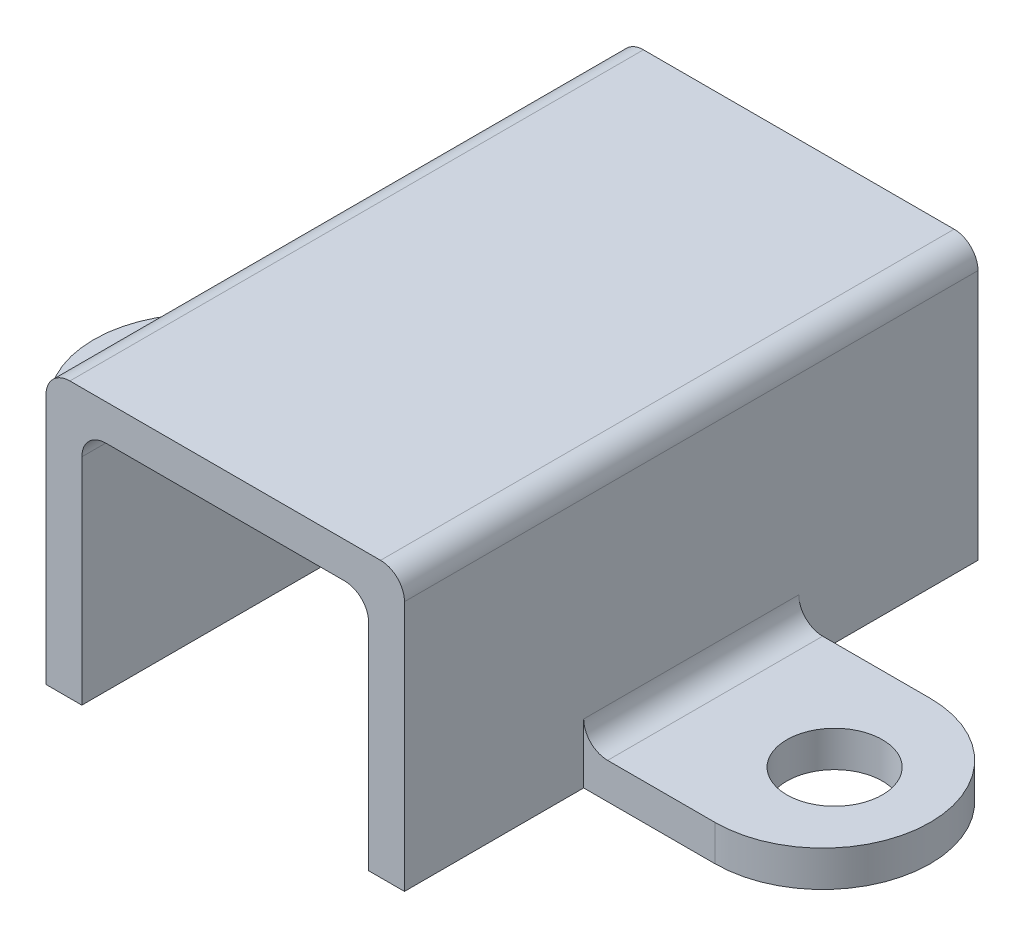
SolidWorks part; units mm, degrees
material "Moldeo de estratificados"
ref_plane "Alzado" through (0, 0, 0) normal (0, 0, 1) x (1, 0, 0)
ref_plane "Planta" through (0, 0, 0) normal (0, 1, 0) x (1, 0, 0)
ref_plane "Vista lateral" through (0, 0, 0) normal (1, 0, 0) x (0, 0, -1)
sketch "Croquis1" plane through (0, 0, 0) normal (0, 0, 1) x (1, 0, 0)
  line L0 (-17.5, -11.5) -> (-17.5, -10)
  line L1 (-17.5, -11.5) -> (-6, -11.5)
  line L2 (-6, -11.5) -> (-6, -1.5)
  line L3 (-6, -1.5) -> (6, -1.5)
  line L4 (6, -1.5) -> (6, -11.5)
  line L5 (6, -11.5) -> (17.5, -11.5)
  line L6 (-17.5, -10) -> (-7.5, -10)
  line L7 (-7.5, -10) -> (-7.5, 0)
  line L8 (-7.5, 0) -> (7.5, 0)
  line L9 (7.5, 0) -> (7.5, -10)
  line L10 (7.5, -10) -> (17.5, -10)
  line L11 (17.5, -10) -> (17.5, -11.5)
  line L12 (0, 6.6473) -> (0, -22.2046) construction
  point P10 (0, 0)
  dimension "D1" = 1.5
  dimension "D2" = 1.5
  dimension "D3" = 1.5
  dimension "D4" = 10
  dimension "D5" = 1.5
  dimension "D6" = 1.5
  dimension "D7" = 6
  dimension "D8" = 17.5
  dimension "D9" = 17.5
extrude "Saliente-Extruir2" add sketch "Croquis1" along normal mid plane 24
sketch "Croquis4" plane through (0, -10, 0) normal (0, 1, 0) x (1, 0, 0)
  line L0 (-28.0622, 0) -> (28.0622, 0) construction
  line L1 (-7.5, 4.5) -> (-7.5, -4.5)
  line L2 (7.5, 4.5) -> (7.5, -4.5)
  line L3 (-7.5, -12) -> (-7.5, 12) construction
  line L4 (7.5, -12) -> (7.5, 12) construction
  line L5 (-7.5, 4.5) -> (-17.5, 4.5)
  line L6 (-17.5, -12) -> (-17.5, 12) construction
  line L7 (-17.5, 4.5) -> (-17.5, -4.5)
  line L8 (-17.5, -4.5) -> (-7.5, -4.5)
  line L9 (-17.5, 12) -> (-7.5, 12)
  line L10 (-7.5, 12) -> (-7.5, 4.5)
  line L11 (-7.5, -4.5) -> (-7.5, -12)
  line L12 (-7.5, -12) -> (-17.5, -12)
  line L13 (-17.5, -12) -> (-17.5, -4.5)
  line L14 (-17.5, 12) -> (-17.5, 4.5)
  line L15 (17.5, 4.5) -> (17.5, -4.5)
  line L16 (7.5, 4.5) -> (17.5, 4.5)
  line L17 (7.5, 4.5) -> (7.5, 12)
  line L18 (7.5, 12) -> (17.5, 12)
  line L19 (17.5, 4.5) -> (17.5, 12)
  line L20 (7.5, -4.5) -> (17.5, -4.5)
  line L21 (7.5, -4.5) -> (7.5, -12)
  line L22 (7.5, -12) -> (17.5, -12)
  line L23 (17.5, -4.5) -> (17.5, -12)
  circle A0 centre (-13.5, 0) radius 2
  circle A1 centre (13.5, 0) radius 2
  point P9 (7.5, 0)
  point P10 (0, 0)
  point P11 (-7.5, 0)
  line M3 (-7.5, 12) -> (-17.5, 12)
  line M4 (-17.5, 12) -> (-17.5, -12)
  line M5 (-17.5, -12) -> (-7.5, -12)
  line M6 (-7.5, -12) -> (-7.5, 12)
  dimension "D1" = 4
  dimension "D2" = 13.5
  dimension "D3" = 13.5
  dimension "D4" = 9
extrude "Cortar-Extruir2" cut sketch "Croquis4" against normal through all contours L5 M6 M3 M4 | L16 L19 L18 L17 | L23 L20 L21 L22 | L8 M4 M5 M6 region at (-12.5, -10, -8.25) region at (-12.5, -10, 8.25) region at (12.5, -10, -8.25) region at (12.5, -10, 8.25)
sketch "Croquis6" plane through (0, -10, 0) normal (0, 1, 0) x (1, 0, 0)
  line L0 (-21.4058, 0) -> (22.0654, 0) construction
  circle A0 centre (-13.5, 0) radius 2
  circle A1 centre (13.5, 0) radius 2
  dimension "D1" = 4
  dimension "D2" = 13.5
  dimension "D3" = 13.5
extrude "Cortar-Extruir3" cut sketch "Croquis6" against normal through all
sketch "Croquis7" plane through (0, -10, 0) normal (0, 1, 0) x (1, 0, 0)
  line L0 (-13, 0) -> (-5.034, 0) construction
  line L6 (-17.5, -4.5) -> (-17.5, 4.5) construction
  line L7 (-13, 4.5) -> (-17.5, 4.5)
  line L8 (-17.5, 4.5) -> (-17.5, 0)
  line L9 (-17.5, 4.5) -> (-13, 4.5)
  line L10 (-17.5, 0) -> (-17.5, -4.5)
  line L11 (-17.5, -4.5) -> (-13, -4.5)
  line L12 (-13, -4.5) -> (-17.5, -4.5)
  line L13 (13, 0) -> (7.5, 0) construction
  line L14 (7.5, -4.5) -> (7.5, 4.5) construction
  line L17 (17.5, -4.5) -> (17.5, 4.5) construction
  line L18 (13, 4.5) -> (17.5, 4.5)
  line L19 (17.5, 4.5) -> (17.5, 0)
  line L20 (13, -4.5) -> (17.5, -4.5)
  line L21 (17.5, -4.5) -> (17.5, 0)
  line L22 (13, -4.5) -> (17.5, -4.5)
  line L23 (17.5, 4.5) -> (13, 4.5)
  arc A3 (-13, 4.5) -> (-13, -4.5) centre (-13, 0) ccw
  arc A5 (13, -4.5) -> (13, 4.5) centre (13, 0) ccw
  point P2 (-17.5, 0)
  point P4 (-9.017, 0)
  point P11 (-17.5, 0)
  point P25 (10.25, 0)
  point P30 (17.5, 0)
  point P33 (17.5, 0)
  line M16 (-17.5, -4.5) -> (-7.5, -4.5)
  line M18 (-7.5, 4.5) -> (-17.5, 4.5)
  line M19 (-17.5, 4.5) -> (-17.5, -4.5)
  dimension "D1" = 4.5
  dimension "D2" = 4.5
  dimension "D3" = 4.5
extrude "Cortar-Extruir4" cut sketch "Croquis7" against normal through all contours A3 M18 M19 | A3 M19 M16 | A5 L19 L18 | A5 L20 L21 region at (-16.4948, -10, -3.4948) region at (-16.4948, -10, 3.4948) region at (16.4948, -10, 3.4948) region at (16.4948, -10, -3.4948)
fillet "Redondeo1" radius 1 1 edges at (-7.5, -10, 0) type face fillet first side face at (-7.5, -8.25, 0) second side face at (-13.5, -10, 2)
fillet "Redondeo2" radius 1 1 edges at (7.5, -10, 0) type face fillet first side face at (7.5, -8.25, 0) second side face at (13.5, -10, 2)
fillet "Redondeo3" radius 1 1 edges at (-6, -1.5, 0) type face fillet first side face at (-6, -6.5, 0) second side face at (0, -1.5, 0)
fillet "Redondeo4" radius 1 1 edges at (6, -1.5, 0) type face fillet first side face at (0.5, -1.5, 0) second side face at (6, -6.5, 0)
fillet "Redondeo5" radius 1 1 edges at (-7.5, 0, 0) type face fillet first side face at (0, 0, 0) second side face at (-7.5, -8, 0)
fillet "Redondeo6" radius 1 1 edges at (7.5, 0, 0) type face fillet first side face at (0.5, 0, 0) second side face at (7.5, -8, 0)
ref_axis "Eje1" through (0, 0, -12) along (0, 0, 1)
